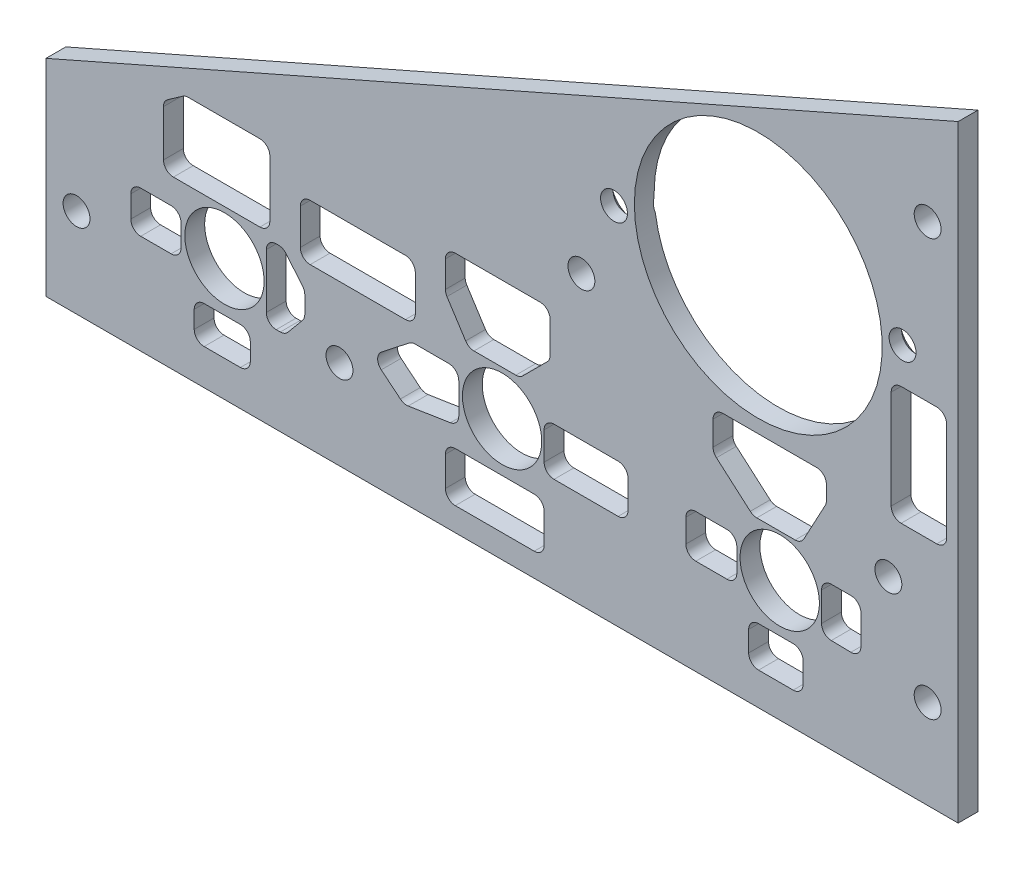
SolidWorks part; units mm, degrees
ref_plane "Front Plane" through (0, 0, 0) normal (0, 0, 1) x (1, 0, 0)
ref_plane "Top Plane" through (0, 0, 0) normal (0, 1, 0) x (1, 0, 0)
ref_plane "Right Plane" through (0, 0, 0) normal (1, 0, 0) x (0, 0, -1)
sketch "Sketch1" plane through (0, 0, 0) normal (0, 0, 1) x (1, 0, 0)
  line L4 (0, 97.282) -> (-146.05, 33.02)
  line L5 (-146.05, 33.02) -> (-146.05, 0)
  line L6 (-146.05, 0) -> (0, 0)
  line L7 (0, 0) -> (0, 97.282)
  line L8 (0, 97.282) -> (-146.05, 33.02)
  line L9 (-146.05, 33.02) -> (-146.05, 0)
  line L10 (-146.05, 0) -> (0, 0)
  line L11 (0, 0) -> (0, 97.282)
  dimension "D1" = 0
extrude "Boss-Extrude1" add sketch "Sketch1" against normal blind 3.175
hole_wizard "#6 Clearance Hole1" positions "Sketch6" profile "Sketch5" hole size "#6" standard "ANSI Inch" end condition through all
sketch "Sketch6" plane through (0, 0, -3.175) normal (0, 0, -1) x (-1, 0, 0)
  point P1 (4.8895, 80.9625)
  point P4 (4.8895, 14.2875)
  point P7 (141.1605, 14.2875)
  point P10 (11.176, 28.575)
  point P12 (60.325, 46.0375)
  point P14 (99.06, 14.2875)
sketch "Sketch5" plane through (-4.8895, 80.9625, -3.175) normal (1, 0, 0) x (0, 1, 0)
  line L0 (0, 0) -> (0, 3.175)
  line L1 (0, 3.175) -> (2.1526, 3.175)
  line L2 (2.1526, 3.175) -> (2.1526, 0)
  line L5 (2.1526, 0) -> (0, 0)
  line L11 (0, -6.35) -> (0, 107.95) construction
  dimension "Thru Hole Dia." = 4.3053
  dimension "Thru Hole Depth" = 3.175
sketch "Sketch7" plane through (0, 0, -3.175) normal (0, 0, -1) x (-1, 0, 0)
  circle A0 centre (32.004, 59.944) radius 19.8438 construction
  circle A1 centre (32.004, 59.944) radius 19.8438
  circle A2 centre (28.575, 19.3759) radius 6.35
  circle A3 centre (73.025, 19.558) radius 6.35
  circle A4 centre (117.475, 19.558) radius 6.35
  ellipse E0 centre (28.575, 21.3285) end of major axis (30.575, 21.3285) minor radius 1.9526 construction
  dimension "D1" = 12.7
extrude "Cut-Extrude1" cut sketch "Sketch7" against normal through all
hole_wizard "CSK for #6 Flat Head Machine Screw (100)1" positions "Sketch8" profile "Sketch9" countersink size "#6" standard "ANSI Inch" end condition up to next
sketch "Sketch8" plane through (0, 0, -3.175) normal (0, 0, -1) x (-1, 0, 0)
  point P0 (8.904, 61.8383)
  point P2 (55.104, 58.0497)
sketch "Sketch9" plane through (-8.904, 61.8383, -3.175) normal (1, 0, 0) x (0, 1, 0)
  line L0 (0, 0) -> (0, 3.175)
  line L1 (0, 3.175) -> (2.1526, 3.175)
  line L2 (2.1526, 3.175) -> (2.1526, 1.1669)
  line L3 (2.1526, 1.1669) -> (3.5433, 0)
  line L5 (3.5433, 0) -> (0, 0)
  line L6 (-2.1526, 1.1669) -> (-3.5433, 0) construction
  line L11 (0, -6.35) -> (0, 107.95) construction
  dimension "Thru Hole Dia." = 4.3053
  dimension "Thru Hole Depth" = 3.175
  dimension "Near C'Sink Dia." = 7.0866
  dimension "Near C'Sink Angle" = 100
sketch "Sketch15" plane through (0, 0, 0) normal (0, 0, -1) x (-1, 0, 0)
  line L0 (3.4308, 55.9821) -> (9.1402, 55.9821)
  line L1 (10.7277, 54.3946) -> (10.7277, 38.5968)
  line L2 (9.1402, 37.0093) -> (3.4308, 37.0093)
  line L3 (1.8433, 38.5968) -> (1.8433, 54.3946)
  line L4 (22.6774, 37.9781) -> (37.6629, 37.9781)
  line L5 (39.2504, 36.3906) -> (39.2504, 32.5074)
  line L6 (38.7044, 31.3093) -> (33.2838, 26.5969)
  line L7 (32.2423, 26.2075) -> (26.1089, 26.2075)
  line L8 (24.7106, 27.0433) -> (21.2791, 33.4267)
  line L9 (21.0899, 34.1784) -> (21.0899, 36.3906)
  line L10 (43.597, 20.6205) -> (43.597, 16.9025)
  line L11 (42.0095, 15.315) -> (37.0319, 15.315)
  line L12 (35.4444, 16.9025) -> (35.4444, 20.6205)
  line L13 (37.0319, 22.208) -> (42.0095, 22.208)
  line L14 (26.4141, 11.6802) -> (31.9586, 11.6802)
  line L15 (33.5461, 10.0927) -> (33.5461, 6.8245)
  line L16 (31.9586, 5.237) -> (26.4141, 5.237)
  line L17 (24.8266, 6.8245) -> (24.8266, 10.0927)
  line L18 (15.5717, 21.3809) -> (15.5717, 16.6831)
  line L19 (17.189, 15.0959) -> (20.3219, 15.1547)
  line L20 (21.8797, 16.7419) -> (21.8797, 21.3809)
  line L21 (20.2922, 22.9684) -> (17.1592, 22.9684)
  line L22 (54.4437, 22.9684) -> (64.7085, 22.9684)
  line L23 (66.296, 21.3809) -> (66.296, 16.9025)
  line L24 (64.7085, 15.315) -> (54.4437, 15.315)
  line L25 (52.8562, 16.9025) -> (52.8562, 21.3809)
  line L26 (67.8835, 11.6802) -> (80.5164, 11.6802)
  line L27 (82.1039, 10.0927) -> (82.1039, 5.3526)
  line L28 (80.5164, 3.7651) -> (67.8835, 3.7651)
  line L29 (66.296, 5.3526) -> (66.296, 10.0927)
  line L30 (79.9618, 21.3647) -> (79.9618, 16.4346)
  line L31 (81.3042, 14.8661) -> (88.0551, 13.8113)
  line L32 (89.3075, 14.1528) -> (92.372, 16.6689)
  line L33 (92.3433, 19.1457) -> (87.9131, 22.6146)
  line L34 (86.9344, 22.9522) -> (81.5493, 22.9522)
  line L35 (65.3361, 37.1822) -> (65.3361, 32.1953)
  line L36 (65.801, 31.0728) -> (69.703, 27.1708)
  line L37 (70.8256, 26.7058) -> (77.5253, 26.7058)
  line L38 (78.8606, 27.4347) -> (81.8516, 32.0861)
  line L39 (82.1039, 32.9447) -> (82.1039, 37.1822)
  line L40 (80.5164, 38.7697) -> (66.9236, 38.7697)
  line L41 (86.9196, 32.8897) -> (86.9196, 27.1599)
  line L42 (88.5071, 25.5724) -> (103.7481, 25.5724)
  line L43 (105.3356, 27.1599) -> (105.3356, 32.8897)
  line L44 (103.7481, 34.4772) -> (88.5071, 34.4772)
  line L45 (110.2115, 37.4103) -> (110.2115, 28.3414)
  line L46 (111.799, 26.7539) -> (125.6537, 26.7539)
  line L47 (127.2412, 28.3414) -> (127.2412, 35.7322)
  line L48 (126.5641, 37.0327) -> (124.167, 38.7108)
  line L49 (123.2566, 38.9978) -> (111.799, 38.9978)
  line L50 (126.0132, 15.9333) -> (130.8857, 15.9333)
  line L51 (132.4732, 17.5208) -> (132.4732, 21.0234)
  line L52 (130.8857, 22.6109) -> (126.0132, 22.6109)
  line L53 (124.4257, 21.0234) -> (124.4257, 17.5208)
  line L54 (114.9274, 11.6802) -> (120.7304, 11.6802)
  line L55 (122.3179, 10.0927) -> (122.3179, 7.3067)
  line L56 (120.7304, 5.7192) -> (114.9274, 5.7192)
  line L57 (113.3399, 7.3067) -> (113.3399, 10.0927)
  line L58 (110.7762, 15.4245) -> (110.7762, 24.1408)
  line L59 (109.1887, 25.7283) -> (108.8288, 25.7283)
  line L60 (107.6065, 25.1537) -> (104.9817, 21.986)
  line L61 (104.6165, 20.9731) -> (104.6165, 18.2321)
  line L62 (104.9816, 17.2192) -> (107.3081, 14.4116)
  line L63 (108.5304, 13.837) -> (109.1887, 13.837)
  line L64 (0, 0) -> (0, 97.282) construction
  line L65 (0, 0) -> (146.05, 0) construction
  arc A1 (104.6165, 18.2321) -> (104.9816, 17.2192) centre (106.204, 18.2321) ccw
  arc A2 (104.9817, 21.986) -> (104.6165, 20.9731) centre (106.204, 20.9731) ccw
  arc A3 (107.3081, 14.4116) -> (108.5304, 13.837) centre (108.5304, 15.4245) ccw
  arc A4 (110.7762, 24.1408) -> (109.1887, 25.7283) centre (109.1887, 24.1408) ccw
  arc A5 (108.8288, 25.7283) -> (107.6065, 25.1537) centre (108.8288, 24.1408) ccw
  arc A6 (110.7762, 15.4245) -> (109.1887, 13.837) centre (109.1887, 15.4245) cw
  arc A7 (126.0132, 22.6109) -> (124.4257, 21.0234) centre (126.0132, 21.0234) ccw
  arc A8 (132.4732, 21.0234) -> (130.8857, 22.6109) centre (130.8857, 21.0234) ccw
  arc A9 (130.8857, 15.9333) -> (132.4732, 17.5208) centre (130.8857, 17.5208) ccw
  arc A10 (126.0132, 15.9333) -> (124.4257, 17.5208) centre (126.0132, 17.5208) cw
  arc A11 (124.167, 38.7108) -> (123.2566, 38.9978) centre (123.2566, 37.4103) ccw
  arc A12 (125.6537, 26.7539) -> (127.2412, 28.3414) centre (125.6537, 28.3414) ccw
  arc A13 (127.2412, 35.7322) -> (126.5641, 37.0327) centre (125.6537, 35.7322) ccw
  arc A14 (110.2115, 28.3414) -> (111.799, 26.7539) centre (111.799, 28.3414) ccw
  arc A15 (105.3356, 32.8897) -> (103.7481, 34.4772) centre (103.7481, 32.8897) ccw
  arc A16 (110.2115, 37.4103) -> (111.799, 38.9978) centre (111.799, 37.4103) cw
  arc A17 (103.7481, 25.5724) -> (105.3356, 27.1599) centre (103.7481, 27.1599) ccw
  arc A18 (86.9196, 27.1599) -> (88.5071, 25.5724) centre (88.5071, 27.1599) ccw
  arc A19 (86.9196, 32.8897) -> (88.5071, 34.4772) centre (88.5071, 32.8897) cw
  arc A20 (82.1039, 37.1822) -> (80.5164, 38.7697) centre (80.5164, 37.1822) ccw
  arc A21 (77.5253, 26.7058) -> (78.8606, 27.4347) centre (77.5253, 28.2933) ccw
  arc A22 (81.8516, 32.0861) -> (82.1039, 32.9447) centre (80.5164, 32.9447) ccw
  arc A23 (69.703, 27.1708) -> (70.8256, 26.7058) centre (70.8256, 28.2933) ccw
  arc A24 (65.3361, 32.1953) -> (65.801, 31.0728) centre (66.9236, 32.1953) ccw
  arc A25 (87.9131, 22.6146) -> (86.9344, 22.9522) centre (86.9344, 21.3647) ccw
  arc A26 (65.3361, 37.1822) -> (66.9236, 38.7697) centre (66.9236, 37.1822) cw
  arc A27 (88.0551, 13.8113) -> (89.3075, 14.1528) centre (88.3002, 15.3797) ccw
  arc A28 (92.372, 16.6689) -> (92.3433, 19.1457) centre (91.3646, 17.8958) ccw
  arc A29 (79.9618, 16.4346) -> (81.3042, 14.8661) centre (81.5493, 16.4346) ccw
  arc A30 (79.9618, 21.3647) -> (81.5493, 22.9522) centre (81.5493, 21.3647) cw
  arc A31 (66.296, 16.9025) -> (64.7085, 15.315) centre (64.7085, 16.9025) cw
  arc A32 (54.4437, 15.315) -> (52.8562, 16.9025) centre (54.4437, 16.9025) cw
  arc A33 (64.7085, 22.9684) -> (66.296, 21.3809) centre (64.7085, 21.3809) cw
  arc A34 (21.8797, 21.3809) -> (20.2922, 22.9684) centre (20.2922, 21.3809) ccw
  arc A35 (54.4437, 22.9684) -> (52.8562, 21.3809) centre (54.4437, 21.3809) ccw
  arc A36 (20.3219, 15.1547) -> (21.8797, 16.7419) centre (20.2922, 16.7419) ccw
  arc A37 (15.5717, 16.6831) -> (17.189, 15.0959) centre (17.1592, 16.6831) ccw
  arc A38 (15.5717, 21.3809) -> (17.1592, 22.9684) centre (17.1592, 21.3809) cw
  arc A39 (33.5461, 6.8245) -> (31.9586, 5.237) centre (31.9586, 6.8245) cw
  arc A40 (26.4141, 5.237) -> (24.8266, 6.8245) centre (26.4141, 6.8245) cw
  arc A41 (31.9586, 11.6802) -> (33.5461, 10.0927) centre (31.9586, 10.0927) cw
  arc A42 (26.4141, 11.6802) -> (24.8266, 10.0927) centre (26.4141, 10.0927) ccw
  arc A43 (35.4444, 20.6205) -> (37.0319, 22.208) centre (37.0319, 20.6205) cw
  arc A44 (37.0319, 15.315) -> (35.4444, 16.9025) centre (37.0319, 16.9025) cw
  arc A45 (43.597, 16.9025) -> (42.0095, 15.315) centre (42.0095, 16.9025) cw
  arc A46 (43.597, 20.6205) -> (42.0095, 22.208) centre (42.0095, 20.6205) ccw
  arc A47 (21.2791, 33.4267) -> (21.0899, 34.1784) centre (22.6774, 34.1784) cw
  arc A48 (26.1089, 26.2075) -> (24.7106, 27.0433) centre (26.1089, 27.795) cw
  arc A49 (39.2504, 32.5074) -> (38.7044, 31.3093) centre (37.6629, 32.5074) cw
  arc A50 (33.2838, 26.5969) -> (32.2423, 26.2075) centre (32.2423, 27.795) cw
  arc A51 (37.6629, 37.9781) -> (39.2504, 36.3906) centre (37.6629, 36.3906) cw
  arc A52 (3.4308, 37.0093) -> (1.8433, 38.5968) centre (3.4308, 38.5968) cw
  arc A53 (22.6774, 37.9781) -> (21.0899, 36.3906) centre (22.6774, 36.3906) ccw
  arc A54 (10.7277, 38.5968) -> (9.1402, 37.0093) centre (9.1402, 38.5968) cw
  arc A55 (9.1402, 55.9821) -> (10.7277, 54.3946) centre (9.1402, 54.3946) cw
  arc A56 (3.4308, 55.9821) -> (1.8433, 54.3946) centre (3.4308, 54.3946) ccw
  arc A57 (114.9274, 5.7192) -> (113.3399, 7.3067) centre (114.9274, 7.3067) cw
  arc A58 (122.3179, 7.3067) -> (120.7304, 5.7192) centre (120.7304, 7.3067) cw
  arc A59 (120.7304, 11.6802) -> (122.3179, 10.0927) centre (120.7304, 10.0927) cw
  arc A60 (114.9274, 11.6802) -> (113.3399, 10.0927) centre (114.9274, 10.0927) ccw
  arc A61 (82.1039, 5.3526) -> (80.5164, 3.7651) centre (80.5164, 5.3526) cw
  arc A62 (67.8835, 3.7651) -> (66.296, 5.3526) centre (67.8835, 5.3526) cw
  arc A63 (80.5164, 11.6802) -> (82.1039, 10.0927) centre (80.5164, 10.0927) cw
  arc A64 (67.8835, 11.6802) -> (66.296, 10.0927) centre (67.8835, 10.0927) ccw
  point P134 (21.8797, 22.9684)
  point P139 (21.8797, 15.1839)
  point P150 (33.5461, 11.6802)
  point P159 (43.597, 15.315)
  point P196 (82.1039, 11.6802)
  point P199 (109.2529, 13.837)
  point P203 (107.3081, 14.4116)
  point P209 (107.6065, 25.1537)
  dimension "D1" = 1.5875
extrude "Cut-Extrude4" cut sketch "Sketch15" along normal through all
